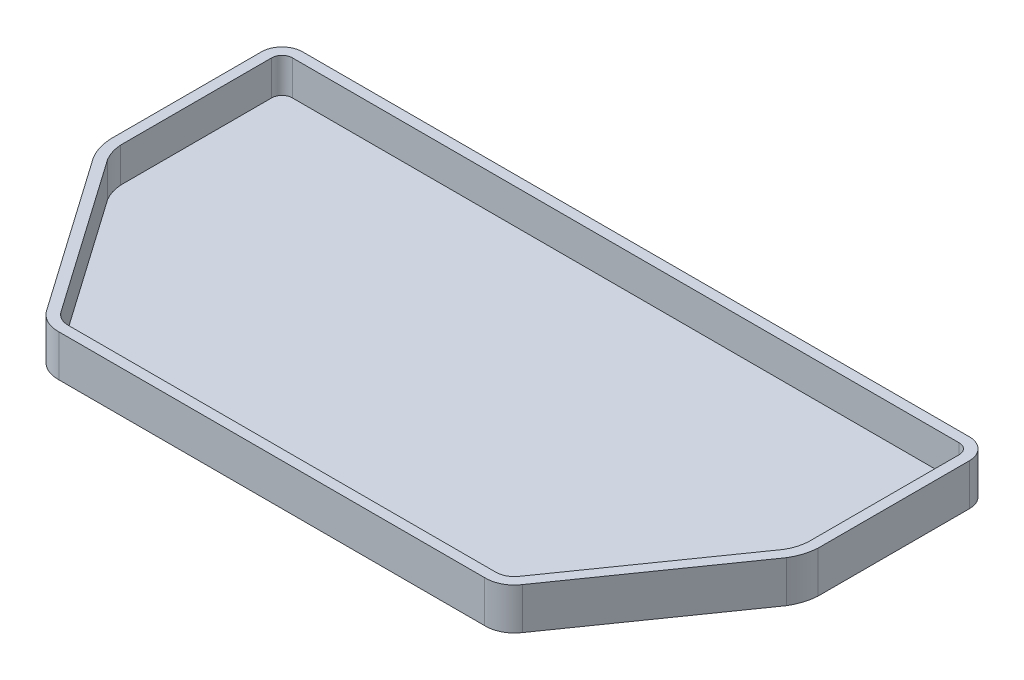
SolidWorks part; units mm, degrees
ref_plane "前视基准面" through (0, 0, 0) normal (0, 0, 1) x (1, 0, 0)
ref_plane "上视基准面" through (0, 0, 0) normal (0, 1, 0) x (1, 0, 0)
ref_plane "右视基准面" through (0, 0, 0) normal (1, 0, 0) x (0, 0, -1)
other "Configuration Table"
sketch "草图1" plane through (0, 0, 0) normal (0, 1, 0) x (1, 0, 0)
  line L0 (0, 0) -> (0, -3) construction
  line L1 (0, -3) -> (3, -3) construction
  line L2 (0, 0) -> (3, 0) construction
  line L3 (0, -3) -> (0, -47)
  line L4 (0, -47) -> (0, -50) construction
  line L5 (0, -50) -> (0, -100) construction
  line L6 (0, -100) -> (35, -100) construction
  line L7 (0, -50) -> (35, -100) construction
  line L8 (35, -100) -> (38, -100) construction
  line L9 (33.2796, -97.5423) -> (1.7204, -52.4577)
  line L10 (38, -100) -> (162, -100)
  line L11 (162, -100) -> (165, -100) construction
  line L12 (165, -100) -> (200, -100) construction
  line L13 (200, -100) -> (200, -50) construction
  line L14 (200, -50) -> (165, -100) construction
  line L15 (200, -50) -> (200, -47) construction
  line L16 (198.2796, -52.4577) -> (166.7204, -97.5423)
  line L17 (200, -47) -> (200, -3)
  line L18 (200, -3) -> (200, 0) construction
  line L19 (200, -3) -> (197, -3) construction
  line L20 (200, 0) -> (197, 0) construction
  line L21 (197, 0) -> (3, 0)
  line L22 (197, 3) -> (3, 3)
  line L23 (-3, -3) -> (-3, -47.1005)
  line L24 (30.7969, -99.2269) -> (-0.7949, -54.0957)
  line L25 (38.0436, -103) -> (161.9564, -103)
  line L26 (200.7949, -54.0957) -> (169.2031, -99.2269)
  line L27 (203, -47.1005) -> (203, -3)
  arc A0 (0, -3) -> (3, 0) centre (3, -3) cw
  arc A1 (0, -47) -> (1.7204, -52.4577) centre (0, -50) cw construction
  arc A2 (0, -47) -> (1.7204, -52.4577) centre (2.8612, -49.0981) cw construction
  arc A3 (0, -47) -> (1.7204, -52.4577) centre (6.2451, -48.0314) cw construction
  arc A4 (0, -47) -> (1.7204, -52.4577) centre (12.282, -46.1284) ccw
  arc A5 (38, -100) -> (33.2796, -97.5423) centre (35, -100) ccw construction
  arc A6 (38, -100) -> (33.2796, -97.5423) centre (36.3854, -97.3391) ccw construction
  arc A7 (38, -100) -> (33.2796, -97.5423) centre (37.8228, -94.5784) cw
  arc A8 (162, -100) -> (166.7204, -97.5423) centre (165, -100) cw construction
  arc A9 (162, -100) -> (166.7204, -97.5423) centre (163.6146, -97.3391) cw construction
  arc A10 (162, -100) -> (166.7204, -97.5423) centre (162.1772, -94.5784) ccw
  arc A11 (200, -47) -> (198.2796, -52.4577) centre (200, -50) ccw construction
  arc A12 (200, -47) -> (198.2796, -52.4577) centre (197.1388, -49.0981) ccw construction
  arc A13 (200, -47) -> (198.2796, -52.4577) centre (193.7549, -48.0314) ccw construction
  arc A14 (200, -47) -> (198.2796, -52.4577) centre (187.718, -46.1284) cw
  arc A15 (200, -3) -> (197, 0) centre (197, -3) ccw
  arc A16 (-3, -3) -> (3, 3) centre (3, -3) cw
  arc A17 (-3, -47.1005) -> (-0.7949, -54.0957) centre (12.282, -46.1284) ccw
  arc A18 (38.0436, -103) -> (30.7969, -99.2269) centre (37.8228, -94.5784) cw
  arc A19 (161.9564, -103) -> (169.2031, -99.2269) centre (162.1772, -94.5784) ccw
  arc A20 (203, -47.1005) -> (200.7949, -54.0957) centre (187.718, -46.1284) cw
  arc A21 (203, -3) -> (197, 3) centre (197, -3) ccw
  dimension "D1" = 3
  dimension "D2" = 3
  dimension "D3" = 3
  dimension "D4" = 44
  dimension "D5" = 3
  dimension "D6" = 50
  dimension "D7" = 35
  dimension "D8" = 3
  dimension "D9" = 124
  dimension "D10" = 3
  dimension "D11" = 35
  dimension "D12" = 50
  dimension "D13" = 3
  dimension "D14" = 44
  dimension "D15" = 3
  dimension "D16" = 3
  dimension "D17" = 3
  dimension "D18" = 3
extrude "凸台-拉伸1" add sketch "草图1" against normal blind 2 contours L22 A16 L23 A17 L24 A18 L25 A19 L26 A20 L27 A21
extrude "凸台-拉伸2" add sketch "草图1<3>" along normal blind 10.1
sketch "草图1<3>" plane through (0, 0, 0) normal (0, 1, 0) x (1, 0, 0) same geometry as "草图1"
